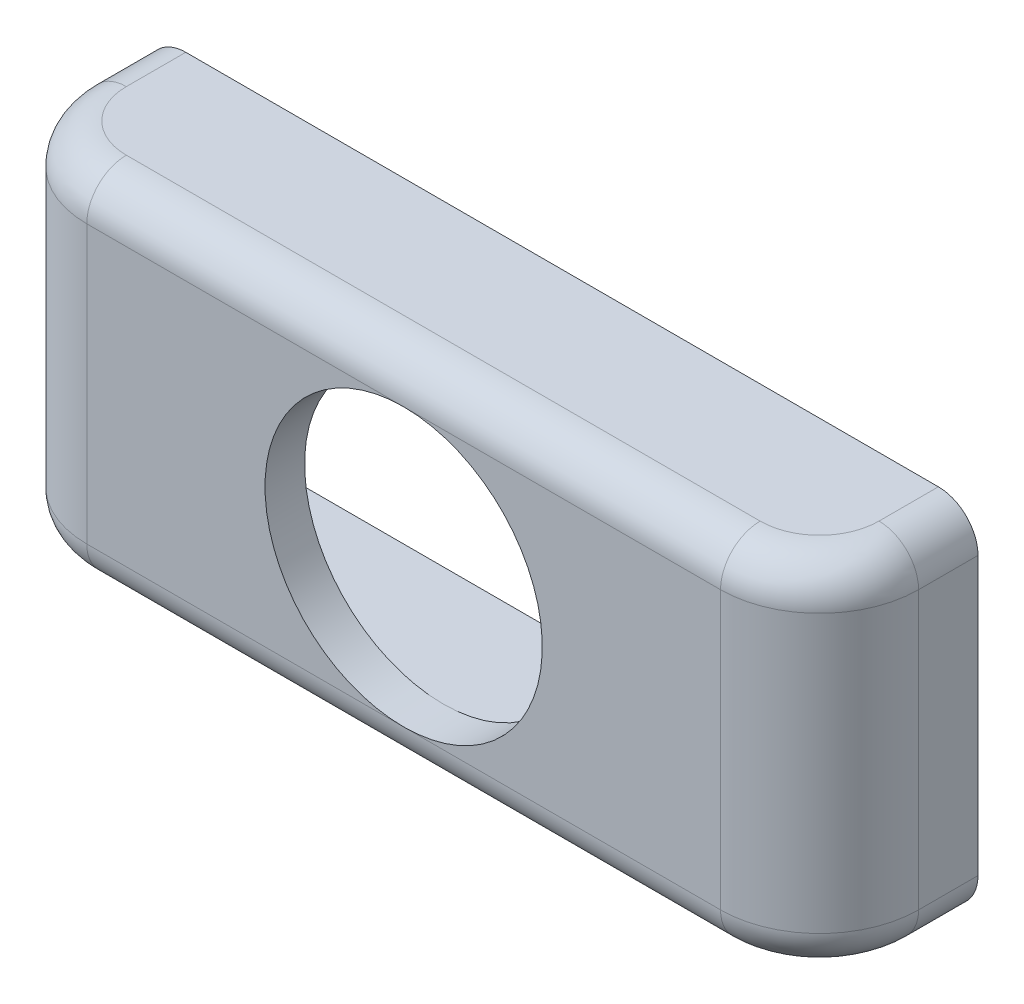
SolidWorks part; units mm, degrees
ref_plane "Front Plane" through (0, 0, 0) normal (0, 0, 1) x (1, 0, 0)
ref_plane "Top Plane" through (0, 0, 0) normal (0, 1, 0) x (1, 0, 0)
ref_plane "Right Plane" through (0, 0, 0) normal (1, 0, 0) x (0, 0, -1)
sketch "Sketch1" plane through (0, 0, 0) normal (0, 0, 1) x (1, 0, 0)
  line L0 (21, 9) -> (-21, -9) construction
  line L1 (-21, 9) -> (21, 9)
  line L2 (-21, 9) -> (-21, -9)
  line L3 (-21, -9) -> (21, -9)
  line L4 (21, 9) -> (21, -9)
  dimension "D1" = 42
  dimension "D2" = 18
extrude "Boss-Extrude1" add sketch "Sketch1" along normal blind 8 contours L1 L4 L3 L2
fillet "Fillet1" radius 5 2 edges at (-21, 0, 8) (21, 0, 8)
fillet "Fillet2" radius 2 10 edges at (-21, -9, 1.5) (-19.5355, -9, 6.5355) (21, -9, 1.5) (19.5355, -9, 6.5355) (-21, 9, 1.5) (-19.5355, 9, 6.5355) (21, 9, 1.5) (19.5355, 9, 6.5355) (0, -9, 8) (0, 9, 8)
shell "Shell1" thickness 2 removed face at (0, 0, 0)
sketch "Sketch2" plane through (0, 0, 8) normal (0, 0, 1) x (1, 0, 0)
  circle A0 centre (0, 0) radius 7
  dimension "D1" = 14
extrude "Cut-Extrude1" cut sketch "Sketch2" against normal through all
